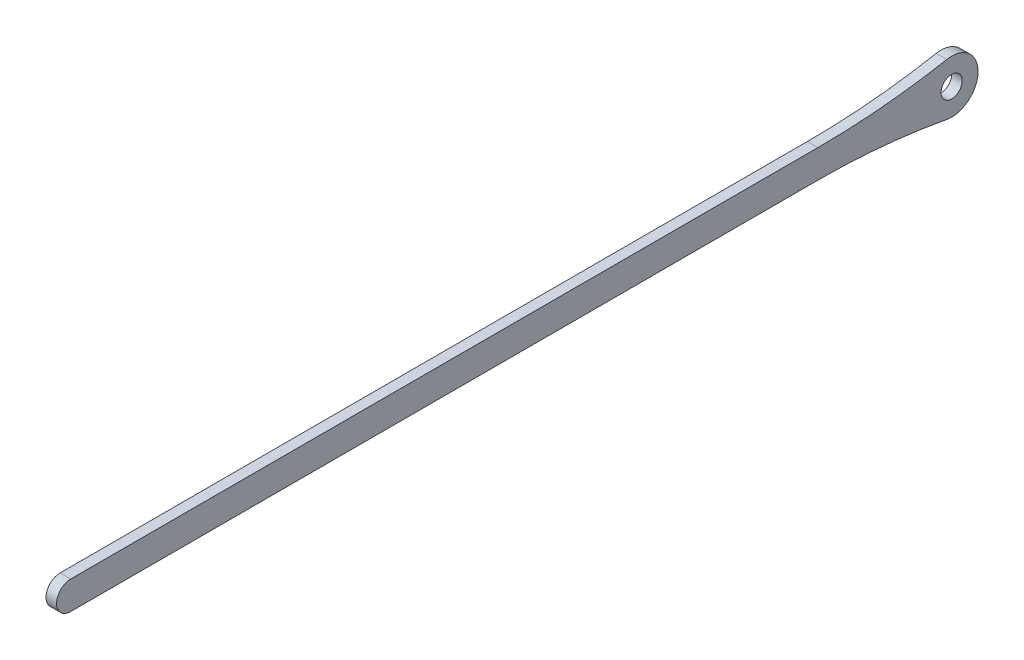
SolidWorks part; units mm, degrees
material "A2017"
ref_plane "正面" through (0, 0, 0) normal (0, 0, 1) x (1, 0, 0)
ref_plane "平面" through (0, 0, 0) normal (0, 1, 0) x (1, 0, 0)
ref_plane "右側面" through (0, 0, 0) normal (1, 0, 0) x (0, 0, -1)
sketch "ｽｹｯﾁ1" plane through (0, 0, 0) normal (1, 0, 0) x (0, 0, -1)
  circle A0 centre (0, 0) radius 3
  circle A1 centre (0, 0) radius 7.5
  dimension "D1" = 6
  dimension "D2" = 15
extrude "ﾎﾞｽ - 押し出し1" add sketch "ｽｹｯﾁ1" along normal mid plane 3
sketch "ｽｹｯﾁ2" plane through (1.5, 0, 0) normal (1, 0, 0) x (0, 0, -1)
  line L0 (0, 0) -> (-250, 0) construction
  line L1 (0, -4) -> (-250, -4)
  line L2 (0, 4) -> (-250, 4)
  arc A1 (0, -4) -> (0, 4) centre (0, 0) ccw
  arc A2 (-250, 4) -> (-250, -4) centre (-250, 0) ccw
  circle A4 centre (0, 0) radius 7.5
  circle A5 centre (0, 0) radius 7.5
  point P0 (-125, 0)
  circle M7 centre (0, 0) radius 7.5
  dimension "D1" = 8
  dimension "D2" = 250
  dimension "D3" = 0
extrude "ﾎﾞｽ - 押し出し2" add sketch "ｽｹｯﾁ2" against normal through all contours L2 A2 L1 A5 M7 region at (1.5, 0, 130.1359)
fillet "ﾌｨﾚｯﾄ1" radius 200 2 edges at (0, -4, 6.3443) (0, 4, 6.3443)
